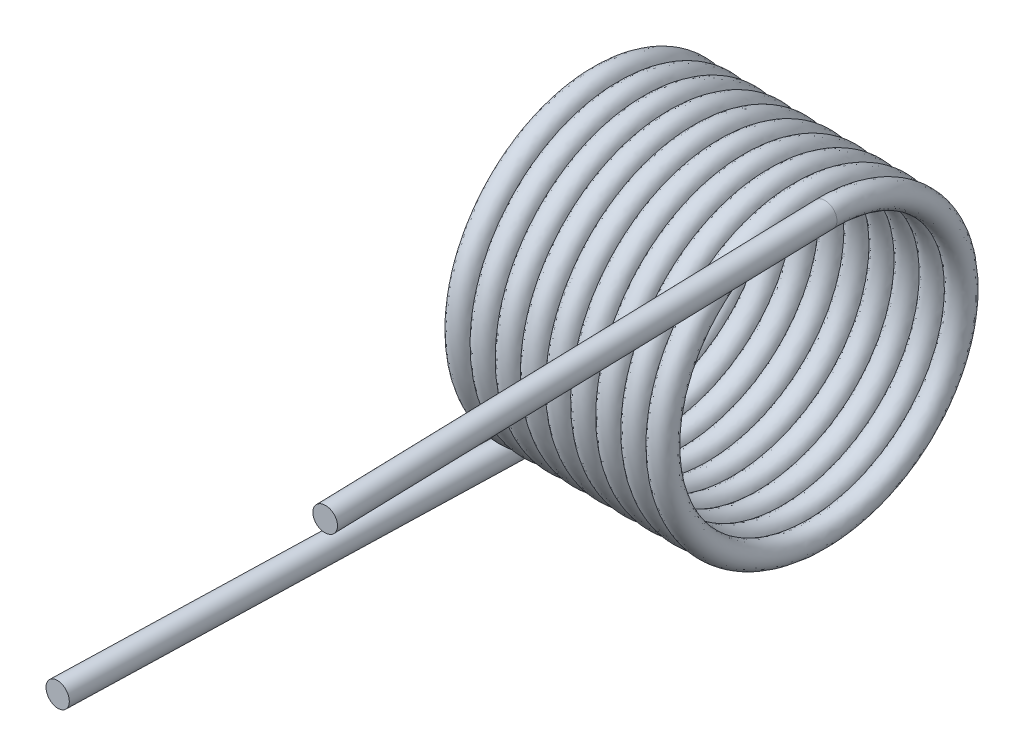
SolidWorks part; units mm, degrees
note: '?' marks a value the reader was unsure of.
ref_plane "Front" through (0, 0, 0) normal (0, 0, 1) x (1, 0, 0)
ref_plane "Top" through (0, 0, 0) normal (0, 1, 0) x (1, 0, 0)
ref_plane "Right" through (0, 0, 0) normal (1, 0, 0) x (0, 0, -1)
sketch "Sketch1" plane through (0, 0, 0) normal (1, 0, 0) x (0, 0, -1)
  line L0 (0, 0) -> (0, -2.9083) construction
  line L1 (0, -2.9083) -> (0, -3.175) construction
  line L2 (0, -3.175) -> (0, -3.4417) construction
  circle A0 centre (0, 0) radius 2.9083 construction
  circle A1 centre (0, 0) radius 3.4417 construction
  circle A2 centre (0, 0) radius 3.175
  circle A3 centre (0, -3.175) radius 0.2667 construction
  circle A4 centre (0, 0) radius 2.3749 construction
  dimension "Wire Dia" = 0.5334
curve "Helix/Spiral1" pitch 0.5588 height 5.3086 turns 9.5
ref_plane "Plane1" through (0, -3.175, 0) normal (0.028, 0, -0.9996) x (0.9982, 0.0534, 0.028)
sketch "Sketch2" plane through (0, -3.175, 0) normal (0.028, 0, -0.9996) x (0.9982, 0.0534, 0.028)
  circle A0 centre (0, 0) radius 0.2667
  dimension "D1" = 0.5334
sweep "Sweep1" add profiles "Sketch2" path "Helix/Spiral1"
sketch "Sketch3" plane through (0, 0, 0) normal (-0.028, 0, 0.9996) x (-0.9982, -0.0534, -0.028)
  circle A1 centre (0.1695, 3.1705) radius 0.2667
  circle A2 centre (0.1695, 3.1705) radius 0.2667
  dimension "D1" = 0
extrude "Extrude1" add sketch "Sketch3" along normal blind 11.43
sketch "Sketch4" plane through (0.0042, 0, 0.1486) normal (0.028, 0, 0.9996) x (0.9994, 0.018, -0.028)
  circle A1 centre (5.3628, 3.079) radius 0.2667
  circle A2 centre (5.3628, 3.079) radius 0.2667
  dimension "D1" = 0
extrude "Extrude2" add sketch "Sketch4" along normal blind 11.43
sketch "Sketch5" plane through (0, 0, 0) normal (1, 0, 0) x (0, 0, -1)
  circle A0 centre (0, 0) radius 2.3749 construction
  circle A1 centre (0, 0) radius 2.3749
ref_axis "Axis1" through (-1.341, 0, 0) along (1, 0, 0)?
equation "\"D4@Helix/Spiral1\"=\"Wire Dia@Sketch1\"+.001"
equation "\"D1@Sketch2\"=\"Wire Dia@Sketch1\""
equation "\"D1@Extrude2\"=\"Leg Length@Extrude1\""
